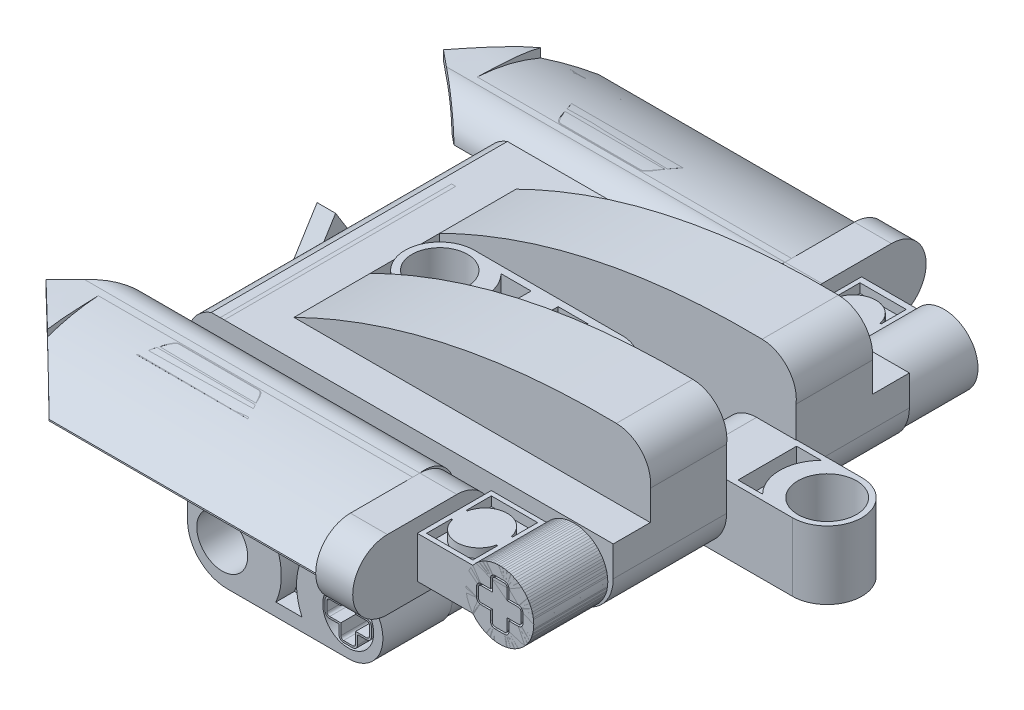
SolidWorks part; units mm, degrees
ref_plane "Front Plane" through (0, 0, 0) normal (0, 0, 1) x (1, 0, 0)
ref_plane "Top Plane" through (0, 0, 0) normal (0, 1, 0) x (1, 0, 0)
ref_plane "Right Plane" through (0, 0, 0) normal (1, 0, 0) x (0, 0, -1)
sketch "Sketch1" plane through (0, 0, 0) normal (0, 0, 1) x (1, 0, 0)
  line L0 (0, 0) -> (20.4999, 0) construction
  line L1 (-1.703, 3.2123) -> (3.2362, 3.2189)
  line L2 (3.2362, -4.283) -> (37.4724, -4.2638)
  line L3 (37.9947, 0) -> (37.9947, 6.9528) construction
  line L5 (41.7362, 0.0024) -> (41.7362, 6.4724)
  line L7 (3.2362, -4.283) -> (3.2362, -14.2852)
  line L8 (-4.2638, 0.0024) -> (-4.2638, -17.5214)
  line L9 (6.293, -18.0352) -> (15.1267, -18.0352) construction
  line L10 (3.2362, -14.2852) -> (13.0975, -14.2852)
  line L11 (0, -21.7852) -> (13.0975, -21.7852)
  arc A8 (-1.703, 3.2123) -> (-4.2638, 0.0024) centre (-0.3807, -0.4691) ccw
  arc A9 (-4.2638, -17.5214) -> (0, -21.7852) centre (0, -17.5214) ccw
  arc A10 (41.7362, 0.0024) -> (37.4724, -4.2638) centre (37.47, 0.0024) cw
  arc A11 (13.0975, -14.2852) -> (13.0975, -21.7852) centre (13.0975, -18.0352) cw
  arc A12 (38.0754, 10.7241) -> (41.7362, 6.4724) centre (37.9947, 6.9528) cw
  spline S0 degree 2 poles (38.0754, 10.7241) (19.0929, 11.058) (3.2362, 3.2189) knots 0 0 0 0.804972 0.804972 0.804972
  point P3 (18.7362, 0)
  point P8 (37.4724, 6.5798)
  point P15 (0.7666, 3.2156)
  point P22 (6.5488, -17.5214)
  dimension "D6" = 7.5
  dimension "D1" = 46
  dimension "D3" = 7.5
  dimension "D5" = 7.5
extrude "Boss-Extrude2" add sketch "Sketch1" against normal blind 32
sketch "Sketch2" plane through (-0.0043, 3.2145, 0) normal (-0.0013, 1, 0) x (1, 0.0013, 0)
  line L0 (3.2405, 32) -> (3.2405, 0) construction
  line L1 (3.2405, 4) -> (47.3557, 4)
  line L2 (3.2405, 4) -> (3.2405, 0)
  line L3 (3.2405, 0) -> (47.3557, 0)
  line L4 (47.3557, 4) -> (47.3557, 0)
  line L6 (3.2405, 32) -> (46.3643, 32)
  line L7 (3.2405, 32) -> (3.2405, 28)
  line L8 (3.2405, 28) -> (46.3643, 28)
  line L9 (46.3643, 32) -> (46.3643, 28)
  dimension "D1" = 4
  dimension "D2" = 43.1238
  dimension "D3" = 44.1152
extrude "Cut-Extrude1" cut sketch "Sketch2" along normal blind 12
sketch "Sketch3" plane through (-0.0043, 3.2145, 0) normal (-0.0013, 1, 0) x (1, 0.0013, 0)
  line L0 (-1.6987, 32) -> (-1.6987, 0) construction
  line L1 (3.2405, 19.75) -> (41.7761, 19.75)
  line L3 (3.2405, 12.25) -> (41.7761, 12.25)
  line L4 (41.7761, 19.75) -> (41.7761, 12.25)
  line L5 (3.2405, 15.574) -> (41.7761, 12.25) construction
  line L6 (3.2405, 16.426) -> (41.7761, 19.75) construction
  line L7 (41.7761, 4) -> (41.7761, 28) construction
  line L9 (3.2405, 28) -> (3.2405, 4) construction
  line L10 (3.2405, 19.75) -> (3.2405, 12.25)
  point P0 (-1.6987, 16)
  dimension "D1" = 7.5
extrude "Cut-Extrude2" cut sketch "Sketch3" against normal mid plane 22
sketch "Sketch4" plane through (-4.2638, 0, 0) normal (-1, 0, 0) x (0, 0, 1)
  line L0 (-32, 0.0024) -> (0, 0.0024) construction
  line L1 (-24.5, 0.0024) -> (-7.5, 0.0024)
  line L2 (-24.5, 0.0024) -> (-24.5, -21.7852)
  line L3 (-24.5, -21.7852) -> (-7.5, -21.7852)
  line L4 (-7.5, 0.0024) -> (-7.5, -21.7852)
  line L5 (-16, -17.5214) -> (-16, -16.5855) construction
  line L6 (-32, -17.5214) -> (0, -17.5214) construction
  line L7 (-32, -21.7852) -> (0, -21.7852) construction
  point P10 (-16, 0.0024)
  dimension "D1" = 17
extrude "Cut-Extrude3" cut sketch "Sketch4" against normal blind 7.5
sketch "Sketch6" plane through (0, 0, -19.75) normal (0, 0, 1) x (1, 0, 0)
  line L0 (3.2362, 3.2189) -> (3.2462, -4.283)
  arc A0 (3.2362, 3.2189) -> (3.2462, -4.283) centre (1.969, -0.5338) cw
sketch "Sketch7" plane through (0, 0, 0) normal (0, 0, 1) x (1, 0, 0)
  line L0 (3.2362, 3.2189) -> (3.2462, -4.283) construction
  arc A0 (3.2412, -0.5321) -> (-4.2638, -0.5321) centre (-0.5113, -0.5305) cw
  arc A1 (-4.2638, -0.5321) -> (3.2412, -0.5321) centre (-0.5113, -0.5321) cw
  point P7 (-0.5113, -4.283)
extrude "Boss-Extrude5" add sketch "Sketch7" against normal blind 25
sketch "Sketch9" plane through (3.2362, 0, 0) normal (-1, 0, 0) x (0, 0, 1)
  line L1 (-24.5, -14.2852) -> (-7.5, -14.2852)
  line L2 (-24.5, -14.2852) -> (-24.5, -21.7852)
  line L3 (-24.5, -21.7852) -> (-7.5, -21.7852)
  line L4 (-7.5, -14.2852) -> (-7.5, -21.7852)
extrude "Cut-Extrude5" cut sketch "Sketch9" against normal through all contours L2 L1 L4 L3
sketch "Sketch10" plane through (0, 0, -24.5) normal (0, 0, 1) x (1, 0, 0)
  line L0 (-0.3012, -18.0352) -> (13.0975, -18.0352) construction
  line L1 (-0.3012, -14.3655) -> (13.0975, -14.3655)
  line L2 (-0.3012, -21.7049) -> (13.0975, -21.7049)
  line L3 (3.2362, -0.724) -> (3.2362, -4.283) construction
  arc A0 (-0.3012, -14.3655) -> (-0.3012, -21.7049) centre (-0.3012, -18.0352) ccw
  arc A1 (13.0975, -21.7049) -> (13.0975, -14.3655) centre (13.0975, -18.0352) ccw
  point P3 (6.3981, -18.0352)
  dimension "D1" = 3.6697
  dimension "D2" = 3.162
extrude "Boss-Extrude6" add sketch "Sketch10" along normal blind 4 separate body contours L2 A1 L1 A0
sketch "Sketch11" plane through (0, 0, -7.5) normal (0, 0, -1) x (-1, 0, 0)
  line L0 (-13.0988, -17.989) -> (0.3, -17.989) construction
  line L1 (-13.0988, -14.3193) -> (0.3, -14.3193)
  line L2 (-13.0988, -21.6588) -> (0.3, -21.6588)
  line L3 (4.2638, -17.5214) -> (4.2638, -0.5321) construction
  arc A0 (-13.0988, -14.3193) -> (-13.0988, -21.6588) centre (-13.0988, -17.989) ccw
  arc A1 (0.3, -21.6588) -> (0.3, -14.3193) centre (0.3, -17.989) ccw
  point P2 (-6.3994, -17.989)
  dimension "D1" = 3.6697
  dimension "D2" = 3.9638
  dimension "D3" = 17.3626
  dimension "D4" = 17.4569
extrude "Boss-Extrude7" add sketch "Sketch11" along normal blind 4 separate body contours L1 A1 L2 A0
sketch "Sketch12" plane through (0, 0, -11.5) normal (0, 0, -1) x (-1, 0, 0)
  circle A0 centre (0.3, -17.989) radius 3.6697
  dimension "D1" = 7.3395
extrude "Boss-Extrude8" add sketch "Sketch12" along normal blind 14 separate body
ref_plane "Plane1" through (0, -21.8193, 0) normal (0, 1, 0) x (1, 0, 0)
sketch "Sketch13" plane through (0, -21.8193, 0) normal (0, 1, 0) x (1, 0, 0)
  circle A0 centre (-0.3, 15.9967) radius 4.4722
  dimension "D1" = 8.9444
  dimension "D2" = 15.9967
extrude "Boss-Extrude9" add sketch "Sketch13" along normal blind 7.5 separate body
sketch "Sketch14" plane through (0, -14.3193, 0) normal (0, 1, 0) x (1, 0, 0)
  circle A0 centre (-0.3, 15.9967) radius 2.5
  dimension "D1" = 5
extrude "Boss-Extrude10" add sketch "Sketch14" along normal blind 10 separate body
sketch "Sketch15" plane through (-4.2638, 0, 0) normal (-1, 0, 0) x (0, 0, 1)
  line L0 (-32, 0.0024) -> (-24.5, 0.0024) construction
  line L1 (-32, 3.2123) -> (0, 3.2123) construction
  line L2 (-16, 3.2123) -> (-25.9602, -12.7877)
  line L3 (-25.9602, -12.7877) -> (-6.0398, -12.7877)
  line L4 (-6.0398, -12.7877) -> (-16, 3.2123)
  line L5 (-24.5, -0.5321) -> (-24.5, -17.5214) construction
  point P4 (-16, -12.7877)
  dimension "D1" = 18.4602
  dimension "D2" = 12.7901
extrude "Boss-Extrude11" add sketch "Sketch15" along normal blind 2 separate body
sketch "Sketch16" plane through (0, 0, 0) normal (0, 1, 0) x (1, 0, 0)
  line L0 (41.7669, 19.75) -> (41.7669, 12.25) construction
  line L1 (6.9862, 16) -> (22.9862, 16) construction
  line L2 (6.9862, 19.75) -> (22.9862, 19.75)
  line L3 (6.9862, 12.25) -> (22.9862, 12.25)
  line L4 (3.2362, 19.75) -> (38.0754, 19.75) construction
  line L5 (3.2362, 19.75) -> (3.2362, 12.25) construction
  arc A0 (6.9862, 19.75) -> (6.9862, 12.25) centre (6.9862, 16) ccw
  arc A1 (22.9862, 12.25) -> (22.9862, 19.75) centre (22.9862, 16) ccw
  circle A2 centre (6.9862, 16) radius 3.0003
  circle A3 centre (22.9862, 16) radius 3.0003
  point P4 (41.7669, 16)
  point P5 (-26.9741, 23.1625)
  point P8 (14.9862, 16)
  point P13 (3.2362, 16)
  point P14 (26.7362, 16)
  dimension "D2" = 6.0006
  dimension "D1" = 23.5
extrude "Boss-Extrude12" add sketch "Sketch16" along normal mid plane 7 separate body
sketch "Sketch17" plane through (0, 3.5, 0) normal (0, 1, 0) x (1, 0, 0)
  line L0 (10.6058, 19.0003) -> (13.8584, 19.0003)
  line L1 (10.6058, 12.9997) -> (13.8584, 12.9997)
  line L2 (13.8584, 12.9997) -> (13.8584, 19.0003)
  line L3 (15.3198, 19.75) -> (15.3198, 12.25) construction
  line L4 (3.2362, 19.75) -> (38.0754, 19.75) construction
  line L5 (38.0754, 12.25) -> (3.2362, 12.25) construction
  line L6 (20.0338, 12.9997) -> (16.7812, 12.9997)
  line L7 (20.0338, 19.0003) -> (16.7812, 19.0003)
  line L8 (16.7812, 12.9997) -> (16.7812, 19.0003)
  arc A0 (10.6058, 19.0003) -> (10.6058, 12.9997) centre (7.6055, 16) cw
  arc A1 (20.0338, 19.0003) -> (20.0338, 12.9997) centre (23.0341, 16) ccw
  dimension "D1" = 4.2431
  dimension "D2" = 6.8722
  dimension "D3" = 8.3336
extrude "Cut-Extrude6" cut sketch "Sketch17" against normal blind 2 contours L2 L0 A0 L1 | L6 L8 L7 A1
sketch "Sketch18" plane through (0, 0, 0) normal (0, 0, 1) x (1, 0, 0)
  line L1 (0, -21.7852) -> (13.0975, -21.7852) construction
  line L3 (34.5641, 1.6807) -> (28.5641, 1.6807)
  line L5 (34.5641, -2.8193) -> (28.5641, -2.8193)
  line L6 (28.5641, 1.6807) -> (28.5641, -2.8193)
  arc A0 (34.5641, -2.8193) -> (34.5641, 1.6807) centre (37.4724, -0.5693) ccw
  point P3 (33.7953, -0.5693)
  dimension "D1" = 7.3541
  dimension "D2" = 21.2159
  dimension "D3" = 6
  dimension "D4" = 4.5
  dimension "D5" = 2.25
extrude "Boss-Extrude13" add sketch "Sketch18" along normal blind 8 separate body
sketch "Sketch19" plane through (28.5641, 0, 0) normal (-1, 0, 0) x (0, 0, 1)
  line L0 (11.23, -0.5701) -> (3.73, -0.5701) construction
  line L2 (11.23, -4.3201) -> (3.73, -4.3201)
  line L3 (11.23, 3.1799) -> (3.73, 3.1799)
  line L4 (0, 1.6807) -> (0, -2.8193) construction
  line L5 (8, -2.8193) -> (0, -2.8193) construction
  arc A0 (11.23, -4.3201) -> (11.23, 3.1799) centre (11.23, -0.5701) ccw
  arc A1 (3.73, 3.1799) -> (3.73, -4.3201) centre (3.73, -0.5701) ccw
  point P4 (7.48, -0.5701)
  point P12 (-0.02, -0.5701)
  point P13 (14.98, -0.5701)
  dimension "D4" = 4.3565
  dimension "D1" = 2.2508
  dimension "D2" = 7.5
  dimension "D3" = 15
extrude "Boss-Extrude14" add sketch "Sketch19" along normal blind 4 separate body
ref_plane "Plane2" through (0, 3.1799, 0) normal (0, 1, 0) x (1, 0, 0)
sketch "Sketch24" plane through (24.5641, 0, 0) normal (-1, 0, 0) x (0, 0, 1)
  line L0 (0, 0) -> (1, 0)
  line L1 (14.0556, -0.9659) -> (15.015, -0.6837)
  arc A0 (11.23, -4.3201) -> (11.23, 3.1799) centre (11.23, -0.5701) ccw construction
  arc A1 (3.73, 3.1799) -> (0, 0) centre (3.2204, 0) ccw
  arc A3 (3.6213, 2.1839) -> (1, 0) centre (3.2204, 0) ccw
  spline S0 degree 3 poles (3.73, 3.1799) (8.4649, 2.9516) (13.8809, 3.1718) (15.015, -0.6837) knots 0 0 0 0 1 1 1 1
  spline S1 degree 1 poles (3.6213, 2.1839) (14.0556, -0.9659) knots 0 0 1 1 construction
  spline S2 degree 3 poles (14.0556, -0.9659) (14.0032, -0.7876) (13.8635, -0.4271) (13.5125, 0.1443) (12.9062, 0.7302) (11.8627, 1.2745) (10.0755, 1.7899) (7.2831, 2.0674) (4.8228, 2.126) (3.6213, 2.1839) knots -0.004259 -0.004259 -0.004259 -0.004259 0.058508 0.121274 0.246806 0.372338 0.497871 0.748935 1 1 1 1
  point P2 (14.98, -0.5701)
  dimension "D1" = 1
extrude "Boss-Extrude16" add sketch "Sketch24" along normal blind 38.4 separate body
sketch "Sketch25" plane through (0, 0, 0) normal (0, 1, 0) x (1, 0, 0)
  line L6 (-13.8359, 0) -> (24.5641, 0) construction
  line L7 (-13.8359, 0) -> (-13.8359, -5.7208)
  line L9 (-7.4819, 0) -> (-13.8359, 0)
  line L10 (-13.8359, 0) -> (24.5641, 0) construction
  line L13 (-13.8359, -5.7208) -> (-7.4819, 0)
  line L14 (-13.8359, -3.73) -> (-13.8359, -15.015) construction
  dimension "D1" = 7.4819
  dimension "D2" = 5.7208
sketch "Sketch27" plane through (0, 0, 0) normal (0, 0, 1) x (1, 0, 0)
  line L0 (-0.5634, -0.5717) -> (8.0611, -0.5717) construction
  line L1 (-0.5634, 3.1368) -> (8.0611, 3.1368)
  line L2 (-0.5634, -4.2803) -> (8.0611, -4.2803)
  line L3 (-4.2638, 0.0024) -> (-4.2638, -17.5214) construction
  line L6 (3.2362, -4.283) -> (37.4724, -4.2638) construction
  arc A0 (-0.5634, 3.1368) -> (-0.5634, -4.2803) centre (-0.5634, -0.5717) ccw
  arc A1 (8.0611, -4.2803) -> (8.0611, 3.1368) centre (8.0611, -0.5717) ccw
  point P2 (-4.272, -0.5717)
  point P3 (3.7488, -0.5717)
  dimension "D1" = 3.7086
  dimension "D2" = 3.7004
  dimension "D3" = 8.0126
extrude "Boss-Extrude17" add sketch "Sketch27" along normal blind 7.5 separate body
sketch "Sketch29" plane through (24.5641, 0, 0) normal (-1, 0, 0) x (0, 0, 1)
  line L0 (3.73, 3.1799) -> (11.23, 3.1799)
  line L1 (11.23, 3.1799) -> (3.73, 3.1799) construction
  arc A0 (3.73, 3.1799) -> (14.98, -0.5701) centre (3.2108, -17.1277) cw
  arc A1 (11.23, 3.1799) -> (14.98, -0.5701) centre (11.23, -0.5701) cw
  arc A2 (11.23, -4.3201) -> (11.23, 3.1799) centre (11.23, -0.5701) ccw construction
extrude "Cut-Extrude13" cut sketch "Sketch29" along normal blind 34
sketch "Sketch30" plane through (24.5641, 0, 0) normal (-1, 0, 0) x (0, 0, 1)
  line L0 (0, 0) -> (0, 3.1908)
  line L1 (0, 3.1908) -> (3.73, 3.1799)
  arc A0 (3.73, 3.1799) -> (0, 0) centre (3.4549, -0.275) ccw
extrude "Cut-Extrude14" cut sketch "Sketch30" along normal blind 34 contours A0 L1 L0 region at (24.5641, 2.4241, 0.7652)
sketch "Sketch31" plane through (0, 0, 8) normal (0, 0, 1) x (1, 0, 0)
  circle A0 centre (37.4724, -0.5693) radius 3.677
  dimension "D1" = 7.3541
extrude "Boss-Extrude18" add sketch "Sketch31" against normal blind 34 separate body
sketch "Sketch33" plane through (0, 0, 8) normal (0, 0, 1) x (1, 0, 0)
  line L0 (37.4724, 3.1077) -> (52.5518, 3.1077)
  line L1 (52.5518, 3.1077) -> (52.5518, -4.2463)
  line L2 (52.5518, -4.2463) -> (37.4724, -4.2638)
  line L3 (37.4724, -4.2638) -> (37.4724, 3.1077)
  circle A0 centre (37.4724, -0.5693) radius 3.677 construction
extrude "Boss-Extrude19" add sketch "Sketch33" against normal blind 7.5 from offset 20.3 separate body offset against normal yes
fillet "Fillet1" 2 edges at (52.5518, -0.5693, -12.3) (52.5518, -0.5693, -19.8) type full round first side face at (45.0121, -0.5737, -12.3) second side face at (45.0121, -0.5737, -19.8) middle face at (52.5518, -0.5693, -16.05)
sketch "Sketch34" plane through (0, 3.1077, 0) normal (0, 1, 0) x (1, 0, 0)
  circle A0 centre (48.8018, 16.05) radius 3.1665
  dimension "D1" = 6.333
extrude "Cut-Extrude15" cut sketch "Sketch34" against normal through all
sketch "Sketch35" plane through (0, 3.1077, 0) normal (0, 1, 0) x (1, 0, 0)
  line L0 (44.9955, 19.2165) -> (42.3329, 19.2165)
  line L1 (42.3329, 19.2165) -> (42.3329, 12.8835)
  line L2 (42.3329, 12.8835) -> (44.9955, 12.8835)
  line L3 (48.8018, 12.3) -> (37.4724, 12.3) construction
  arc A0 (44.9955, 19.2165) -> (44.9955, 12.8835) centre (48.162, 16.05) ccw
  dimension "D1" = 4.4781
  dimension "D2" = 4.8605
  dimension "D3" = 7.5232
  dimension "D4" = 10.6896
  dimension "D5" = 0.5835
extrude "Cut-Extrude16" cut sketch "Sketch35" against normal blind 2
ref_plane "Plane4" through (0, 0, -16) normal (0, 0, 1) x (1, 0, 0)
mirror "Mirror1" about plane through (0, 0, -16) normal (0, 0, 1) of bodies 131 119 120 133
sketch "Sketch37" plane through (0, 1.6807, 0) normal (0, 1, 0) x (1, 0, 0)
  line L0 (28.5641, -8) -> (28.5641, 0) construction
  line L15 (29.0641, -0.5) -> (29.0641, -3.1964)
  line L16 (29.0641, -3.1964) -> (29.1872, -3.1964)
  line L17 (33.9409, -3.1964) -> (34.0641, -3.1964)
  line L18 (34.0641, -3.1964) -> (34.0641, -0.5)
  line L19 (34.0641, -0.5) -> (29.0641, -0.5)
  line L20 (34.0641, -7.5) -> (29.0641, -7.5)
  line L21 (29.0641, -7.5) -> (29.0641, -4.8036)
  line L22 (29.0641, -4.8036) -> (29.1872, -4.8036)
  line L23 (33.9409, -4.8036) -> (34.0641, -4.8036)
  line L24 (34.0641, -4.8036) -> (34.0641, -7.5)
  line L25 (34.5641, 0) -> (28.5641, 0) construction
  arc A3 (29.1872, -3.1964) -> (33.9409, -3.1964) centre (31.5641, -3.6964) cw
  arc A4 (29.1872, -4.8036) -> (33.9409, -4.8036) centre (31.5641, -4.3036) ccw
  dimension "D1" = 2.4289
  dimension "D2" = 0.5
  dimension "D3" = 0.6232
  dimension "D4" = 3
  dimension "D5" = 0.5
  dimension "D6" = 3.1964
  dimension "D7" = 4.3036
extrude "Cut-Extrude18" cut sketch "Sketch37" against normal blind 1 contours L15 L16 A3 L17 L18 L19 | L20 L21 L22 A4 L23 L24
sketch "Sketch38" plane through (0, 1.6807, 0) normal (0, 1, 0) x (1, 0, 0)
  line L0 (29.0334, 39.36) -> (29.0334, 36.6637)
  line L1 (29.0334, 36.6637) -> (29.1566, 36.6637)
  line L2 (33.9103, 36.6637) -> (34.0334, 36.6637)
  line L3 (34.0334, 36.6637) -> (34.0334, 39.36)
  line L4 (34.0334, 39.36) -> (29.0334, 39.36)
  line L5 (34.0334, 32.36) -> (29.0334, 32.36)
  line L6 (29.0334, 32.36) -> (29.0334, 35.0564)
  line L7 (29.0334, 35.0564) -> (29.1566, 35.0564)
  line L8 (33.9103, 35.0564) -> (34.0334, 35.0564)
  line L9 (34.0334, 35.0564) -> (34.0334, 32.36)
  line L10 (34.5641, 40) -> (34.5641, 32) construction
  line L11 (34.5641, 32) -> (28.5641, 32) construction
  arc A0 (29.1566, 36.6637) -> (33.9103, 36.6637) centre (31.5334, 36.1637) cw
  arc A1 (29.1566, 35.0564) -> (33.9103, 35.0564) centre (31.5334, 35.5564) ccw
  dimension "D1" = 2.4289
  dimension "D2" = 0.5306
  dimension "D3" = 0.6538
  dimension "D4" = 3.0306
  dimension "D5" = 0.36
  dimension "D6" = 3.0564
  dimension "D7" = 4.1637
extrude "Cut-Extrude19" cut sketch "Sketch38" against normal blind 1
sketch "Sketch39" plane through (0, 0, 8) normal (0, 0, 1) x (1, 0, 0)
  line L0 (36.4724, -1.5693) -> (36.4724, -2.5693)
  line L1 (37.9724, 1.9307) -> (36.9724, 1.9307)
  line L2 (38.4724, 1.4307) -> (38.4724, 0.4307)
  line L3 (37.9724, -3.0693) -> (36.9724, -3.0693)
  line L4 (36.4724, 1.4307) -> (36.4724, 0.4307)
  line L5 (38.4724, 1.9307) -> (36.4724, -3.0693) construction
  line L6 (38.4724, -3.0693) -> (36.4724, 1.9307) construction
  line L7 (39.4724, 0.4307) -> (38.4724, 0.4307)
  line L8 (39.9724, -0.0693) -> (39.9724, -1.0693)
  line L9 (39.4724, -1.5693) -> (38.4724, -1.5693)
  line L10 (34.9724, -0.0693) -> (34.9724, -1.0693)
  line L11 (39.9724, 0.4307) -> (34.9724, -1.5693) construction
  line L12 (39.9724, -1.5693) -> (34.9724, 0.4307) construction
  line L13 (36.4724, 0.4307) -> (35.4724, 0.4307)
  line L14 (36.4724, -1.5693) -> (35.4724, -1.5693)
  line L15 (38.4724, -1.5693) -> (38.4724, -2.5693)
  line L16 (38.2724, 1.4307) -> (38.2724, 0.2307)
  line L17 (39.4724, 0.2307) -> (38.2724, 0.2307)
  line L18 (39.7724, -0.0693) -> (39.7724, -1.0693)
  line L19 (39.4724, -1.3693) -> (38.2724, -1.3693)
  line L20 (38.2724, -1.3693) -> (38.2724, -2.5693)
  line L21 (37.9724, -2.8693) -> (36.9724, -2.8693)
  line L22 (36.6724, -1.3693) -> (36.6724, -2.5693)
  line L23 (36.6724, -1.3693) -> (35.4724, -1.3693)
  line L24 (35.1724, -0.0693) -> (35.1724, -1.0693)
  line L25 (36.6724, 0.2307) -> (35.4724, 0.2307)
  line L26 (36.6724, 1.4307) -> (36.6724, 0.2307)
  line L27 (37.9724, 1.7307) -> (36.9724, 1.7307)
  line L28 (37.4724, 3.1077) -> (37.4724, 2.3017) construction
  line L29 (41.1494, -0.5693) -> (40.6744, -0.5693) construction
  arc A0 (36.9724, -3.0693) -> (36.4724, -2.5693) centre (36.9724, -2.5693) cw
  arc A1 (38.4724, -2.5693) -> (37.9724, -3.0693) centre (37.9724, -2.5693) cw
  arc A2 (37.9724, 1.9307) -> (38.4724, 1.4307) centre (37.9724, 1.4307) cw
  arc A3 (36.9724, 1.9307) -> (36.4724, 1.4307) centre (36.9724, 1.4307) ccw
  arc A4 (39.4724, 0.4307) -> (39.9724, -0.0693) centre (39.4724, -0.0693) cw
  arc A5 (39.9724, -1.0693) -> (39.4724, -1.5693) centre (39.4724, -1.0693) cw
  arc A6 (35.4724, -1.5693) -> (34.9724, -1.0693) centre (35.4724, -1.0693) cw
  arc A7 (35.4724, 0.4307) -> (34.9724, -0.0693) centre (35.4724, -0.0693) ccw
  arc A8 (39.4724, 0.2307) -> (39.7724, -0.0693) centre (39.4724, -0.0693) cw
  arc A9 (39.7724, -1.0693) -> (39.4724, -1.3693) centre (39.4724, -1.0693) cw
  arc A10 (38.2724, -2.5693) -> (37.9724, -2.8693) centre (37.9724, -2.5693) cw
  arc A11 (36.9724, -2.8693) -> (36.6724, -2.5693) centre (36.9724, -2.5693) cw
  arc A12 (35.4724, -1.3693) -> (35.1724, -1.0693) centre (35.4724, -1.0693) cw
  arc A13 (35.4724, 0.2307) -> (35.1724, -0.0693) centre (35.4724, -0.0693) ccw
  arc A14 (36.9724, 1.7307) -> (36.6724, 1.4307) centre (36.9724, 1.4307) ccw
  arc A15 (37.9724, 1.7307) -> (38.2724, 1.4307) centre (37.9724, 1.4307) cw
  arc A16 (34.5641, -2.8193) -> (34.5641, 1.6807) centre (37.4724, -0.5693) ccw construction
  point P0 (39.3727, -0.3189)
  point P5 (39.3727, -0.3189)
  point P66 (37.4724, -3.0693)
  point P67 (37.4724, -0.5693)
  point P68 (37.4724, -1.0929)
  dimension "D3" = 0.5
  dimension "D1" = 5
  dimension "D2" = 1
  dimension "D4" = 0.2
  dimension "D5" = 0.2
extrude "Cut-Extrude20" cut sketch "Sketch39" against normal through all
sketch "Sketch41" plane through (0, 0, 0) normal (0, 0, 1) x (1, 0, 0)
  circle A0 centre (13.0975, -18.0352) radius 2.75
  dimension "D1" = 5.5
extrude "Cut-Extrude23" cut sketch "Sketch41" against normal through all
sketch "Sketch42" plane through (0, 0, 0) normal (0, 0, 1) x (1, 0, 0)
  line L0 (12.0975, -19.0352) -> (12.0975, -20.0352)
  line L1 (13.5975, -15.5352) -> (12.5975, -15.5352)
  line L2 (14.0975, -16.0352) -> (14.0975, -17.0352)
  line L3 (13.5975, -20.5352) -> (12.5975, -20.5352)
  line L4 (12.0975, -16.0352) -> (12.0975, -17.0352)
  line L5 (14.0975, -15.5352) -> (12.0975, -20.5352) construction
  line L6 (14.0975, -20.5352) -> (12.0975, -15.5352) construction
  line L7 (15.0975, -17.0352) -> (14.0975, -17.0352)
  line L8 (15.5975, -17.5352) -> (15.5975, -18.5352)
  line L9 (15.0975, -19.0352) -> (14.0975, -19.0352)
  line L10 (10.5975, -17.5352) -> (10.5975, -18.5352)
  line L11 (15.5975, -17.0352) -> (10.5975, -19.0352) construction
  line L12 (15.5975, -19.0352) -> (10.5975, -17.0352) construction
  line L13 (12.0975, -17.0352) -> (11.0975, -17.0352)
  line L14 (12.0975, -19.0352) -> (11.0975, -19.0352)
  line L15 (14.0975, -19.0352) -> (14.0975, -20.0352)
  line L16 (13.8975, -16.0352) -> (13.8975, -17.2352)
  line L17 (15.0975, -17.2352) -> (13.8975, -17.2352)
  line L18 (15.3975, -17.5352) -> (15.3975, -18.5352)
  line L19 (15.0975, -18.8352) -> (13.8975, -18.8352)
  line L20 (13.8975, -18.8352) -> (13.8975, -20.0352)
  line L21 (13.5975, -20.3352) -> (12.5975, -20.3352)
  line L22 (12.2975, -18.8352) -> (12.2975, -20.0352)
  line L23 (12.2975, -18.8352) -> (11.0975, -18.8352)
  line L24 (10.7975, -17.5352) -> (10.7975, -18.5352)
  line L25 (12.2975, -17.2352) -> (11.0975, -17.2352)
  line L26 (12.2975, -16.0352) -> (12.2975, -17.2352)
  line L27 (13.5975, -15.7352) -> (12.5975, -15.7352)
  line L28 (34.9724, -0.0693) -> (34.9724, -1.0693) construction
  line L29 (37.9724, 1.9307) -> (36.9724, 1.9307) construction
  line L30 (39.9724, -1.0693) -> (39.9724, -0.0693) construction
  arc A0 (12.5975, -20.5352) -> (12.0975, -20.0352) centre (12.5975, -20.0352) cw
  arc A1 (14.0975, -20.0352) -> (13.5975, -20.5352) centre (13.5975, -20.0352) cw
  arc A2 (13.5975, -15.5352) -> (14.0975, -16.0352) centre (13.5975, -16.0352) cw
  arc A3 (12.5975, -15.5352) -> (12.0975, -16.0352) centre (12.5975, -16.0352) ccw
  arc A4 (15.0975, -17.0352) -> (15.5975, -17.5352) centre (15.0975, -17.5352) cw
  arc A5 (15.5975, -18.5352) -> (15.0975, -19.0352) centre (15.0975, -18.5352) cw
  arc A6 (11.0975, -19.0352) -> (10.5975, -18.5352) centre (11.0975, -18.5352) cw
  arc A7 (11.0975, -17.0352) -> (10.5975, -17.5352) centre (11.0975, -17.5352) ccw
  arc A8 (15.0975, -17.2352) -> (15.3975, -17.5352) centre (15.0975, -17.5352) cw
  arc A9 (15.3975, -18.5352) -> (15.0975, -18.8352) centre (15.0975, -18.5352) cw
  arc A10 (13.8975, -20.0352) -> (13.5975, -20.3352) centre (13.5975, -20.0352) cw
  arc A11 (12.5975, -20.3352) -> (12.2975, -20.0352) centre (12.5975, -20.0352) cw
  arc A12 (11.0975, -18.8352) -> (10.7975, -18.5352) centre (11.0975, -18.5352) cw
  arc A13 (11.0975, -17.2352) -> (10.7975, -17.5352) centre (11.0975, -17.5352) ccw
  arc A14 (12.5975, -15.7352) -> (12.2975, -16.0352) centre (12.5975, -16.0352) ccw
  arc A15 (13.5975, -15.7352) -> (13.8975, -16.0352) centre (13.5975, -16.0352) cw
  arc A16 (13.0975, -21.7852) -> (13.0975, -14.2852) centre (13.0975, -18.0352) ccw construction
  point P0 (0.956, -17.6929)
  point P5 (0.956, -17.6929)
  point P67 (13.0975, -18.0352)
  point P68 (13.0975, -19.2312)
  point P73 (16.8475, -18.0352)
extrude "Boss-Extrude20" add sketch "Sketch42" against normal blind 32 separate body
sketch "Sketch43" plane through (0, 0, 0) normal (0, 0, 1) x (1, 0, 0)
  line L0 (-4.2638, -4.7877) -> (3.2362, -4.7877) construction
  line L1 (-4.2638, -12.7877) -> (-4.2638, 3.2123) construction
  line L2 (3.2362, -14.2852) -> (3.2362, -4.283) construction
  line L3 (39.9724, -1.0693) -> (39.9724, -0.0693) construction
  line L4 (37.9724, 1.9307) -> (36.9724, 1.9307) construction
  circle A1 centre (-0.5138, -17.6466) radius 2.75
  circle A2 centre (-0.5138, -8.7673) radius 2.75
  point P4 (-0.5138, -4.7877)
  dimension "D1" = 5.5
  dimension "D2" = 2
  dimension "D3" = 2
  dimension "D4" = 10.698
  dimension "D5" = 19.5773
extrude "Cut-Extrude24" cut sketch "Sketch43" against normal blind 12
sketch "Sketch45" plane through (0, 0, -32) normal (0, 0, -1) x (-1, 0, 0)
  line L0 (-39.9724, -1.0693) -> (-39.9724, -0.0693) construction
  line L3 (-37.9724, 1.9307) -> (-36.9724, 1.9307) construction
  circle A1 centre (0.5138, -17.2888) radius 2.75
  circle A2 centre (0.5138, -8.5814) radius 2.75
  dimension "D1" = 5.5
  dimension "D2" = 3
  dimension "D3" = 40.4862
  dimension "D4" = 2
  dimension "D5" = 10.5122
  dimension "D6" = 19.2196
extrude "Cut-Extrude25" cut sketch "Sketch45" against normal blind 12
sketch "Sketch46" plane through (0, 0, -32) normal (0, 0, -1) x (-1, 0, 0)
  line L0 (2.9331, -11.6802) -> (2.9331, -14.2802)
  line L1 (-2.0669, -11.6802) -> (-2.0669, -14.2802)
  line L2 (-36.4724, -1.5693) -> (-36.4724, -2.5693) construction
  line L3 (-37.9724, 1.9307) -> (-36.9724, 1.9307) construction
  arc A0 (2.9331, -11.6802) -> (-2.0669, -11.6802) centre (0.4331, -8.5577) cw
  arc A1 (-2.0669, -14.2802) -> (2.9331, -14.2802) centre (0.4331, -17.4027) cw
  dimension "D1" = 4
  dimension "D2" = 34.4055
  dimension "D3" = 36.9055
  dimension "D4" = 3.5
  dimension "D5" = 0.5
  dimension "D6" = 10.4884
  dimension "D7" = 16.2109
extrude "Cut-Extrude26" cut sketch "Sketch46" against normal blind 2
sketch "Sketch47" plane through (0, 0, -32) normal (0, 0, -1) x (-1, 0, 0)
  line L0 (-5.1415, -15.2852) -> (-7.7113, -15.2852)
  line L1 (-7.7113, -20.7852) -> (-5.1415, -20.7852)
  line L2 (-13.0975, -20.7852) -> (-11.7027, -20.7852) construction
  line L3 (-13.0975, -15.2852) -> (-11.4406, -15.2852) construction
  line L4 (2.9331, -14.2802) -> (2.9331, -11.6802) construction
  line L5 (-39.4724, 0.4307) -> (-38.4724, 0.4307) construction
  arc A0 (-7.7113, -15.2852) -> (-7.7113, -20.7852) centre (-13.8704, -18.0352) cw
  arc A1 (-5.1415, -15.2852) -> (-5.1415, -20.7852) centre (1.0176, -18.0352) ccw
  circle A2 centre (-13.0975, -18.0352) radius 2.75 construction
  point P0 (-4.7977, -15.705)
  point P1 (-4.7845, -15.7182)
  dimension "D1" = 6.7451
  dimension "D2" = 1.9155
  dimension "D3" = 10.6444
  dimension "D4" = 12.1109
  dimension "D6" = 41.4055
extrude "Cut-Extrude27" cut sketch "Sketch47" against normal blind 2
sketch "Sketch48" plane through (0, 0, 0) normal (0, 0, 1) x (1, 0, 0)
  line L0 (8.1006, -14.8966) -> (5.2859, -14.8966)
  line L1 (5.2859, -20.3966) -> (8.1006, -20.3966)
  line L2 (-0.5138, -14.8966) -> (0.4042, -14.8966) construction
  line L3 (-0.5138, -20.3966) -> (1.0921, -20.3966) construction
  line L4 (39.9724, -1.0693) -> (39.9724, -0.0693) construction
  line L5 (37.9724, 1.9307) -> (36.9724, 1.9307) construction
  arc A0 (5.2859, -14.8966) -> (5.2859, -20.3966) centre (-0.8732, -17.6466) cw
  arc A1 (8.1006, -14.8966) -> (8.1006, -20.3966) centre (14.2597, -17.6466) ccw
  circle A2 centre (-0.5138, -17.6466) radius 2.75 construction
  circle A3 centre (-0.5138, -17.6466) radius 2.75 construction
  point P0 (6.4974, -15.7088)
  point P1 (6.5106, -15.722)
  dimension "D1" = 6.7451
  dimension "D2" = 2
  dimension "D3" = 25.7127
  dimension "D4" = 34.6865
  dimension "D5" = 2
extrude "Cut-Extrude28" cut sketch "Sketch48" against normal blind 2
sketch "Sketch49" plane through (0, 0, 0) normal (0, 0, 1) x (1, 0, 0)
  line L0 (1.9514, -11.8191) -> (1.9514, -14.5845)
  line L1 (-2.9184, -11.8191) -> (-2.9184, -14.5845)
  line L2 (38.4724, 0.4307) -> (38.4724, 1.4307) construction
  line L3 (37.9724, 1.9307) -> (36.9724, 1.9307) construction
  arc A0 (1.9514, -11.8191) -> (-2.9184, -11.8191) centre (-0.4835, -8.6456) cw
  arc A1 (-2.9184, -14.5845) -> (1.9514, -14.5845) centre (-0.4835, -17.758) cw
  dimension "D1" = 4
  dimension "D2" = 0.5
  dimension "D3" = 36.521
  dimension "D4" = 38.9559
  dimension "D5" = 0.5
  dimension "D6" = 10.5763
  dimension "D7" = 19.6887
extrude "Cut-Extrude29" cut sketch "Sketch49" against normal blind 2
extrude "Cut-Extrude31" cut sketch "Sketch25" along normal blind 12
sketch "Sketch51" plane through (0, 3.1799, 0) normal (0, 1, 0) x (1, 0, 0)
  line L0 (-13.8359, -5.7208) -> (-3.2775, -15.8988)
  line L1 (-13.8359, -5.7208) -> (-13.8359, -15.015) construction
  line L3 (-3.2775, -15.8988) -> (-13.8359, -15.8988)
  line L4 (-13.8359, -15.8988) -> (-13.8359, -5.7208)
  dimension "D1" = 3.2775
  dimension "D2" = 5.7208
extrude "Cut-Extrude41" cut sketch "Sketch51" against normal blind 12
sketch "Sketch53" plane through (0, 0, 0) normal (0, 1, 0) x (1, 0, 0)
  line L0 (-13.8359, 37.22) -> (-7.4819, 32)
  line L1 (-13.8359, 47.015) -> (-13.8359, 35.73) construction
  line L2 (-13.8359, 32) -> (24.5641, 32) construction
  line L3 (-7.4819, 32) -> (-13.8359, 32)
  line L4 (-13.8359, 32) -> (-13.8359, 37.22)
  dimension "D1" = 5.22
extrude "Cut-Extrude42" cut sketch "Sketch53" along normal blind 12
sketch "Sketch54" plane through (0, 0, 0) normal (0, 1, 0) x (1, 0, 0)
  line L0 (-13.8359, 37.22) -> (-6.12, 47.9274)
  line L2 (-6.12, 47.9274) -> (-13.8409, 47.9274)
  line L3 (-13.8409, 47.9274) -> (-13.8359, 37.22)
extrude "Cut-Extrude43" cut sketch "Sketch54" along normal blind 12 and the other way blind 12
